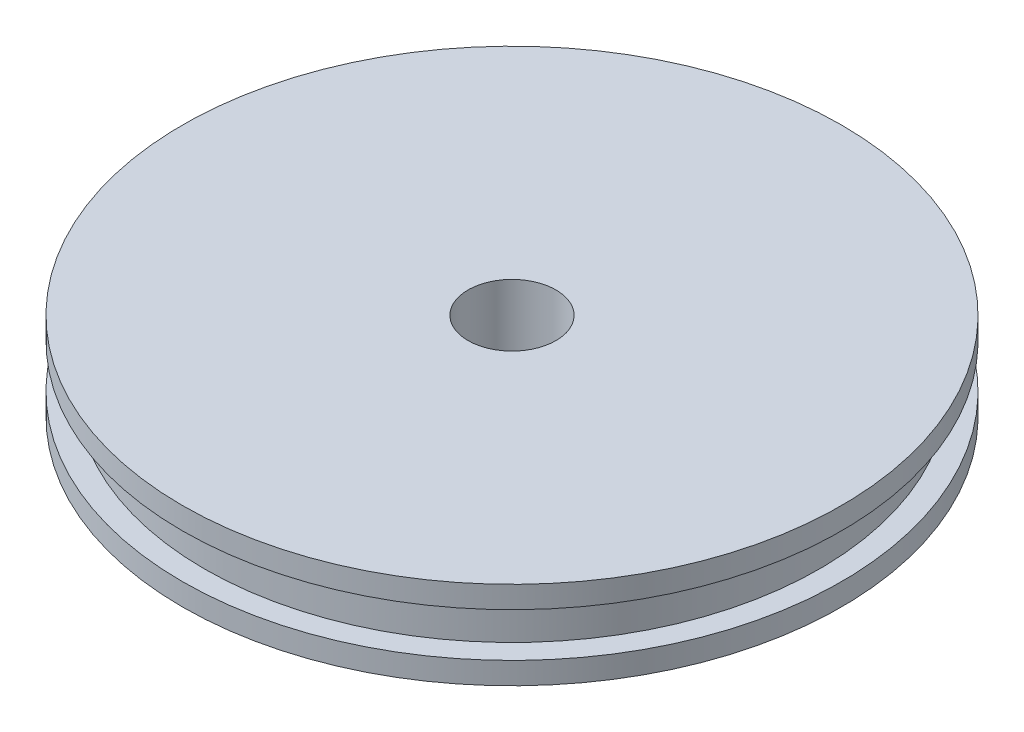
SolidWorks part; units mm, degrees
ref_plane "Front Plane" through (0, 0, 0) normal (0, 0, 1) x (1, 0, 0)
ref_plane "Top Plane" through (0, 0, 0) normal (0, 1, 0) x (1, 0, 0)
ref_plane "Right Plane" through (0, 0, 0) normal (1, 0, 0) x (0, 0, -1)
sketch "Sketch1" plane through (0, 0, 0) normal (0, 1, 0) x (1, 0, 0)
  circle A0 centre (0, 0) radius 37.5
  circle A1 centre (0, 0) radius 35
  circle A2 centre (0, 0) radius 7.5
  circle A3 centre (0, 0) radius 5
  dimension "D1" = 75
  dimension "D2" = 70
  dimension "D3" = 15
  dimension "D4" = 10
extrude "Boss-Extrude2" add sketch "Sketch1" along normal mid plane 5 contours A1 A2 region at (-34.0101, 0, 0)
extrude "Boss-Extrude3" add sketch "Sketch1<10>" along normal blind 2.5 from surface contours A0 A1 | A1 A2 region at (-36.4393, 0, 0) region at (-34.0101, 0, 0) starting at face at (0, 2.5, 7.5)
sketch "Sketch1<10>" plane through (0, 0, 0) normal (0, 1, 0) x (1, 0, 0) same geometry as "Sketch1"
extrude "Boss-Extrude4" add sketch "Sketch1<11>" against normal blind 2.5 from surface separate body contours A1 | A0 starting at face at (0, -2.5, 7.5)
sketch "Sketch1<11>" plane through (0, 0, 0) normal (0, 1, 0) x (1, 0, 0) same geometry as "Sketch1"
extrude "Boss-Extrude6" add sketch "Sketch1<15>" against normal up to surface (5 mm away) contours A1 A2 region at (-34.0101, 0, 0) up to face at (0, -5, 35)
sketch "Sketch1<15>" plane through (0, 0, 0) normal (0, 1, 0) x (1, 0, 0) same geometry as "Sketch1"
extrude "Boss-Extrude7" add sketch "Sketch1<16>" along normal mid plane 10 contours A3 | A2 | A3 region at (0, 0, 0)
sketch "Sketch1<16>" plane through (0, 0, 0) normal (0, 1, 0) x (1, 0, 0) same geometry as "Sketch1"
